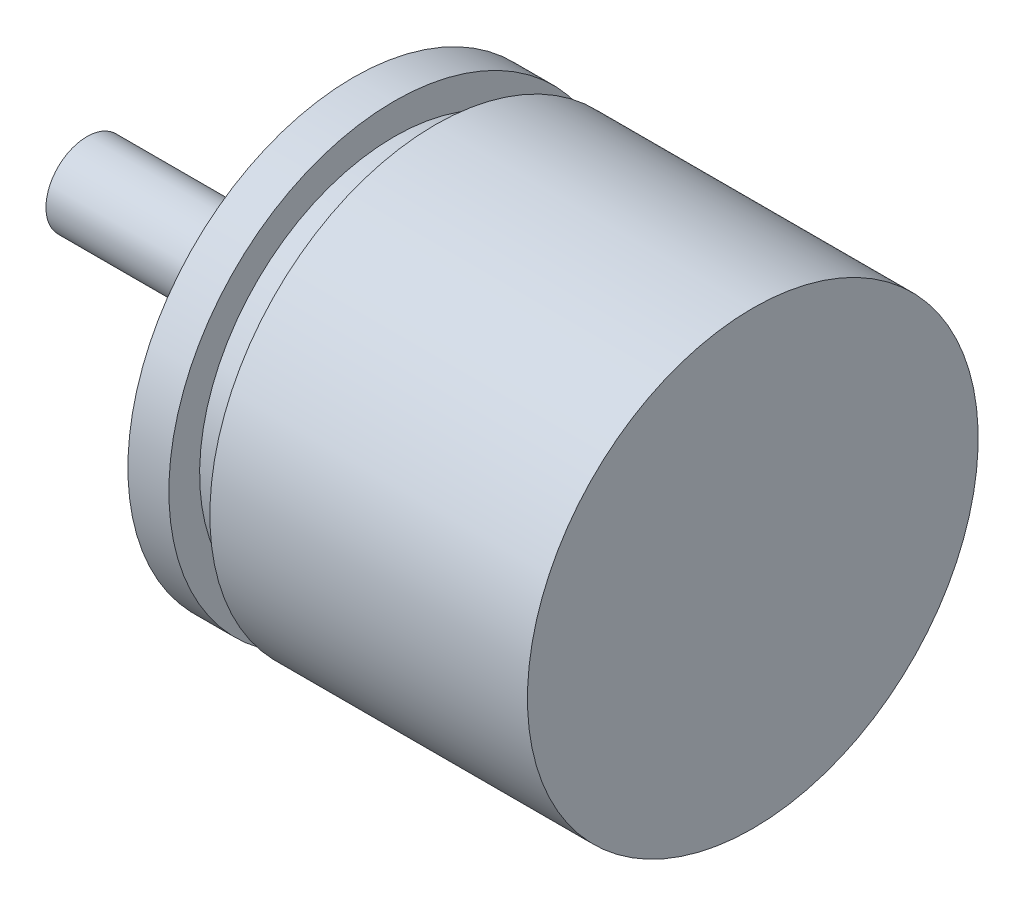
SolidWorks part; units mm, degrees
ref_plane "前视基准面" through (0, 0, 0) normal (0, 0, 1) x (1, 0, 0)
ref_plane "上视基准面" through (0, 0, 0) normal (0, 1, 0) x (1, 0, 0)
ref_plane "右视基准面" through (0, 0, 0) normal (1, 0, 0) x (0, 0, -1)
sketch "草图1" plane through (0, 0, 0) normal (0, 0, 1) x (1, 0, 0)
  line L0 (-15.5, 11) -> (0, 11)
  line L1 (0, 11) -> (0, 0)
  line L2 (-15.5, 11) -> (-15.5, 9.5)
  line L3 (-15.5, 9.5) -> (-17.5, 9.5)
  line L4 (-17.5, 9.5) -> (-17.5, 11)
  line L5 (-17.5, 11) -> (-19.5, 11)
  line L6 (-19.5, 11) -> (-19.5, 4)
  line L7 (-19.5, 4) -> (-20.5, 4)
  line L8 (-20.5, 4) -> (-20.5, 2)
  line L9 (-20.5, 2) -> (-32.5, 2)
  line L10 (-32.5, 2) -> (-32.5, 0)
  line L11 (0, 0) -> (-32.5, 0)
  line L12 (12.9536, 0) -> (2.8627, 0) construction
  dimension "D1" = 15.5
  dimension "D2" = 11
  dimension "D3" = 1.5
  dimension "D4" = 2
  dimension "D5" = 1
  dimension "D6" = 2
  dimension "D7" = 2
  dimension "D8" = 2
  dimension "D9" = 12
revolve "旋转1" add sketch "草图1" angle 360 about L12
ref_plane "基准面1" through (-32.5, 0, 0) normal (-1, 0, 0) x (0, 0, 1)
sketch "草图2" plane through (-32.5, 0, 0) normal (-1, 0, 0) x (0, 0, 1)
  line L0 (0, 0) -> (-1.2, -1.6) construction
  line L1 (0, 0) -> (1.2, -1.6) construction
  line L2 (1.2, -1.6) -> (-1.2, -1.6)
  circle A0 centre (0, 0) radius 2 construction
  arc A1 (-1.2, -1.6) -> (1.2, -1.6) centre (0, 0) ccw
  dimension "D1" = 1.6
extrude "切除-拉伸1" cut sketch "草图2" against normal blind 10
ref_plane "基准面2" through (-19.5, 0, 0) normal (-1, 0, 0) x (0, 0, 1)
sketch "草图3" plane through (-19.5, 0, 0) normal (-1, 0, 0) x (0, 0, 1)
  line L0 (0, 0) -> (-7.5, 0) construction
  circle A0 centre (0, 0) radius 7.5 construction
  circle A1 centre (-7.5, 0) radius 1
  circle A2 centre (0, 0) radius 7.5 construction
  circle A3 centre (3.75, 6.4952) radius 1
  circle A4 centre (0, 0) radius 7.5 construction
  circle A5 centre (3.75, -6.4952) radius 1
  point P13 (0, 0)
  dimension "D1" = 15
  dimension "D2" = 3
  dimension "D3" = 2
extrude "切除-拉伸2" cut sketch "草图3" against normal blind 5
thread "螺纹线1" pitch 0.4 start angle 0, offset 0, length 5, pitch 0.4, diameter 2
ref_plane "基准面3" through (-19.5, 0, -8.5) normal (0, -1, 0) x (0, 0, -1)
sketch "螺纹线轮廓1" plane through (-19.5, 0, -8.5) normal (0, -1, 0) x (0, 0, -1)
  line L0 (0, 0) -> (0, 0.4) construction
  line L1 (0, 0) -> (0.2165, 0.125)
  line L2 (0.2165, 0.125) -> (0.2165, 0.175)
  line L3 (0.2165, 0.175) -> (0, 0.3)
  line L4 (0.2165, 0.15) -> (0, 0.15) construction
  line L11 (0, 0) -> (0, 0.3)
  point P2 (0, 0)
  dimension "Pitch" = 0.4
  dimension "Profile_Angle" = 60
  dimension "Profile_Land" = 0.05
  dimension "Profile_Height" = 0.2165
thread "螺纹线2" pitch 0.4 profile "螺纹线轮廓2" start angle 0, offset 0, length 5, pitch 0.4, diameter 2
ref_plane "基准面4" through (-19.5, 6.4952, 2.75) normal (0, -1, 0) x (0, 0, -1)
sketch "螺纹线轮廓2" plane through (-19.5, 6.4952, 2.75) normal (0, -1, 0) x (0, 0, -1)
  line L0 (0, 0) -> (0, 0.4) construction
  line L1 (0, 0) -> (0.2165, 0.125)
  line L2 (0.2165, 0.125) -> (0.2165, 0.175)
  line L3 (0.2165, 0.175) -> (0, 0.3)
  line L4 (0.2165, 0.15) -> (0, 0.15) construction
  line L11 (0, 0) -> (0, 0.3)
  point P2 (0, 0)
  dimension "Pitch" = 0.4
  dimension "Profile_Angle" = 60
  dimension "Profile_Land" = 0.05
  dimension "Profile_Height" = 0.2165
thread "螺纹线3" pitch 0.4 profile "螺纹线轮廓3" start angle 0, offset 0, length 5, pitch 0.4, diameter 2
ref_plane "基准面5" through (-19.5, -6.4952, 2.75) normal (0, -1, 0) x (0, 0, -1)
sketch "螺纹线轮廓3" plane through (-19.5, -6.4952, 2.75) normal (0, -1, 0) x (0, 0, -1)
  line L0 (0, 0) -> (0, 0.4) construction
  line L1 (0, 0) -> (0.2165, 0.125)
  line L2 (0.2165, 0.125) -> (0.2165, 0.175)
  line L3 (0.2165, 0.175) -> (0, 0.3)
  line L4 (0.2165, 0.15) -> (0, 0.15) construction
  line L11 (0, 0) -> (0, 0.3)
  point P2 (0, 0)
  dimension "Pitch" = 0.4
  dimension "Profile_Angle" = 60
  dimension "Profile_Land" = 0.05
  dimension "Profile_Height" = 0.2165
